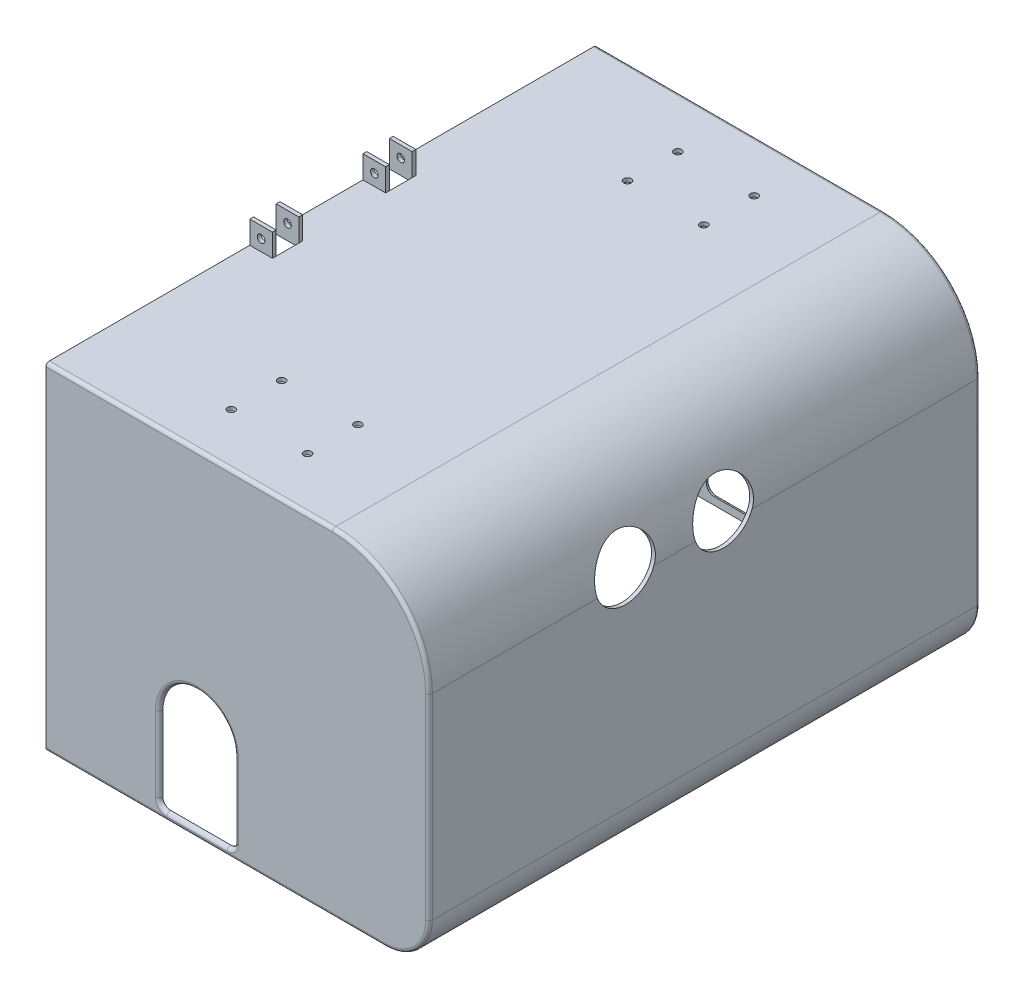
SolidWorks part; units mm, degrees
ref_plane "Front Plane" through (0, 0, 0) normal (0, 0, 1) x (1, 0, 0)
ref_plane "Top Plane" through (0, 0, 0) normal (0, 1, 0) x (1, 0, 0)
ref_plane "Right Plane" through (0, 0, 0) normal (1, 0, 0) x (0, 0, -1)
sketch "Sketch1" plane through (0, 0, 0) normal (0, 0, 1) x (1, 0, 0)
  line L0 (-440.6947, -122.1594) -> (303.3053, -122.1594) construction
  line L1 (0, 0) -> (379.6, 0)
  line L2 (479.6, -100) -> (479.6, -360)
  line L3 (449.6, -390) -> (370, -390)
  arc A0 (379.6, 0) -> (479.6, -100) centre (379.6, -100) cw
  arc A1 (479.6, -360) -> (449.6, -390) centre (449.6, -360) cw
  dimension "D1" = 100
  dimension "D2" = 30
  dimension "D3" = 379.6
  dimension "D4" = 390
  dimension "D5" = 79.6
sketch "Sketch2" plane through (0, 0, 0) normal (1, 0, 0) x (0, 0, -1)
  line L0 (0, 0) -> (0, -100) construction
  line L1 (-360.5, 27.8983) -> (360.5, 27.8983)
  line L2 (-365, 23.3983) -> (-365, 22.8983)
  line L4 (-365, 22.8983) -> (365, 22.8983)
  line L5 (365, 23.3983) -> (365, 22.8983)
  line L6 (-365, 27.8983) -> (365, 22.8983) construction
  line L7 (-365, 22.8983) -> (365, 27.8983) construction
  arc A0 (-360.5, 27.8983) -> (-365, 23.3983) centre (-360.5, 23.3983) ccw
  arc A1 (360.5, 27.8983) -> (365, 23.3983) centre (360.5, 23.3983) cw
  point P0 (0, 25.3983)
  dimension "D3" = 4.5
  dimension "D4" = 4.5
  dimension "D1" = 730
  dimension "D2" = 5
sweep "Sweep2" add profiles "Sketch2" path "Sketch1"
sketch "Sketch3" plane through (0, 27.8983, 0) normal (0, 1, 0) x (1, 0, 0)
  line L0 (0, 360.5) -> (0, -360.5) construction
  line L1 (0, 60) -> (30, 60)
  line L2 (0, 60) -> (0, 90)
  line L3 (0, 90) -> (30, 90)
  line L4 (30, 60) -> (30, 90)
  line L5 (0, 60) -> (0, -60) construction
  line L6 (0, -60) -> (30, -60)
  line L7 (0, -60) -> (0, -90)
  line L8 (0, -90) -> (30, -90)
  line L9 (30, -60) -> (30, -90)
  dimension "D1" = 30
  dimension "D2" = 120
extrude "Cut-Extrude1" cut sketch "Sketch3" against normal blind 10
sketch "Sketch4" plane through (0, 27.8983, 0) normal (0, 1, 0) x (1, 0, 0)
  line L0 (30, -90) -> (30, -60) construction
  line L1 (0, -90) -> (30, -90)
  line L2 (0, -90) -> (0, -95)
  line L3 (0, -95) -> (30, -95)
  line L4 (30, -90) -> (30, -95)
  line L5 (0, 0) -> (71.7722, 0) construction
  line L6 (0, -60) -> (30, -60)
  line L7 (0, -60) -> (0, -55)
  line L8 (0, -55) -> (30, -55)
  line L9 (30, -60) -> (30, -55)
  line L10 (0, 60) -> (0, -60) construction
  line L11 (0, 95) -> (30, 95)
  line L12 (30, 90) -> (30, 95)
  line L13 (0, 90) -> (30, 90)
  line L14 (0, 90) -> (0, 95)
  line L15 (0, 55) -> (30, 55)
  line L16 (30, 60) -> (30, 55)
  line L17 (0, 60) -> (30, 60)
  line L18 (0, 60) -> (0, 55)
  dimension "D1" = 5
extrude "Boss-Extrude1" add sketch "Sketch4" along normal blind 30
sketch "Sketch5" plane through (0, 0, 0) normal (0, 0, 1) x (1, 0, 0)
  line L0 (0, 57.8983) -> (30, 57.8983) construction
  line L2 (0, 57.8983) -> (0, 27.8983) construction
  circle A0 centre (15, 42.8983) radius 5
  dimension "D1" = 10
  dimension "D2" = 15
  dimension "D3" = 15
extrude "Cut-Extrude2" cut sketch "Sketch5" against normal through all both and the other way through all
sketch "Sketch6" plane through (0, 0, 0) normal (1, 0, 0) x (0, 0, -1)
  line L6 (90, 22.8983) -> (365, 22.8983) construction
  line L7 (90, 22.8983) -> (90, 57.8983) construction
  circle A0 centre (-104.5, -85.9017) radius 40
  circle A1 centre (25.5, -85.9017) radius 40
  dimension "D1" = 80
  dimension "D2" = 108.8
  dimension "D3" = 64.5
  dimension "D4" = 130
extrude "Cut-Extrude3" cut sketch "Sketch6" along normal through all
sketch "Sketch9" plane through (0, 0, -365) normal (0, 0, -1) x (-1, 0, 0)
  line L0 (0, 22.8983) -> (-379.6, 22.8983)
  line L1 (-502.4983, -100) -> (-502.4983, -360)
  line L2 (-449.6, -412.8983) -> (-370, -412.8983)
  line L3 (0, -412.8983) -> (0, 22.8983)
  line L4 (-370, -412.8983) -> (-370, -417.8983)
  line L5 (-370, -417.8983) -> (0, -417.8983)
  line L6 (0, -417.8983) -> (0, -412.8983)
  arc A0 (-379.6, 22.8983) -> (-502.4983, -100) centre (-379.6, -100) ccw
  arc A1 (-502.4983, -360) -> (-449.6, -412.8983) centre (-449.6, -360) ccw
extrude "Boss-Extrude3" add sketch "Sketch9" against normal blind 5
mirror "Mirror3" about plane through (0, 0, 0) normal (0, 0, 1) of "Boss-Extrude3"
sketch "Sketch11" plane through (0, 0, 0) normal (0, 0, 1) x (1, 0, 0)
  line L0 (507.4983, -100) -> (507.4983, -360) construction
  line L1 (370, -417.8983) -> (0, -417.8983) construction
  line L2 (149.9983, -297.8983) -> (149.9983, -397.8983)
  line L3 (159.9983, -407.8983) -> (239.9983, -407.8983)
  line L4 (249.9983, -397.8983) -> (249.9983, -297.8983)
  arc A0 (249.9983, -297.8983) -> (149.9983, -297.8983) centre (199.9983, -297.8983) ccw
  arc A1 (239.9983, -407.8983) -> (249.9983, -397.8983) centre (239.9983, -397.8983) ccw
  arc A2 (149.9983, -397.8983) -> (159.9983, -407.8983) centre (159.9983, -397.8983) ccw
  dimension "D3" = 10
  dimension "D5" = 50
  dimension "D1" = 307.5
  dimension "D2" = 120
  dimension "D4" = 100
extrude "Cut-Extrude4" cut sketch "Sketch11" against normal through all both and the other way through all
fillet "Fillet1" radius 5 12 edges at (247.0693, -404.9693, -365) (247.0693, -404.9693, 365) (199.9983, -407.8983, -365) (199.9983, -407.8983, 365) (152.9272, -404.9693, -365) (152.9272, -404.9693, 365) (149.9983, -347.8983, -365) (149.9983, -347.8983, 365) (199.9983, -247.8983, -365) (199.9983, -247.8983, 365) (249.9983, -347.8983, -365) (249.9983, -347.8983, 365)
fillet "Fillet2" radius 4.5 6 edges at (370, -417.8983, -362.75) (370, -415.6483, -365) (185, -417.8983, -365) (370, -415.6483, 365) (185, -417.8983, 365) (370, -417.8983, 362.75)
sketch "Sketch13" plane through (0, 27.8983, 0) normal (0, 1, 0) x (1, 0, 0)
  circle A13 centre (176.3164, -229.1307) radius 5
  circle A14 centre (176.3164, -229.1307) radius 5 construction
  circle A15 centre (277.4164, -295.8693) radius 5
  circle A16 centre (277.4164, -295.8693) radius 5 construction
  circle A18 centre (277.4164, -229.1307) radius 5
  circle A19 centre (277.4164, -229.1307) radius 5 construction
  circle A20 centre (176.3164, -295.8693) radius 5
  circle A21 centre (176.3164, -295.8693) radius 5 construction
  circle A22 centre (277.4164, 229.1307) radius 5
  circle A23 centre (176.3164, 229.1307) radius 5
  circle A24 centre (176.3164, 295.8693) radius 5
  circle A25 centre (277.4164, 295.8693) radius 5
  circle A26 centre (176.3164, 295.8693) radius 5 construction
  circle A27 centre (277.4164, 295.8693) radius 5 construction
  circle A28 centre (277.4164, 229.1307) radius 5 construction
  circle A29 centre (176.3164, 229.1307) radius 5 construction
  dimension "D1" = 10
extrude "Cut-Extrude5" cut sketch "Sketch13" against normal up to next
sketch "Sketch14" plane through (0, -417.8983, 0) normal (0, -1, 0) x (1, 0, 0)
  line L1 (370, -360) -> (370, 360) construction
  line L2 (449.6, 0) -> (370, 0) construction
  line L3 (449.6, -360.5) -> (449.6, 360.5) construction
  circle A2 centre (390, 100) radius 5
  circle A4 centre (390, -100) radius 5
  dimension "D4" = 100
extrude "Cut-Extrude6" cut sketch "Sketch14" against normal up to next
